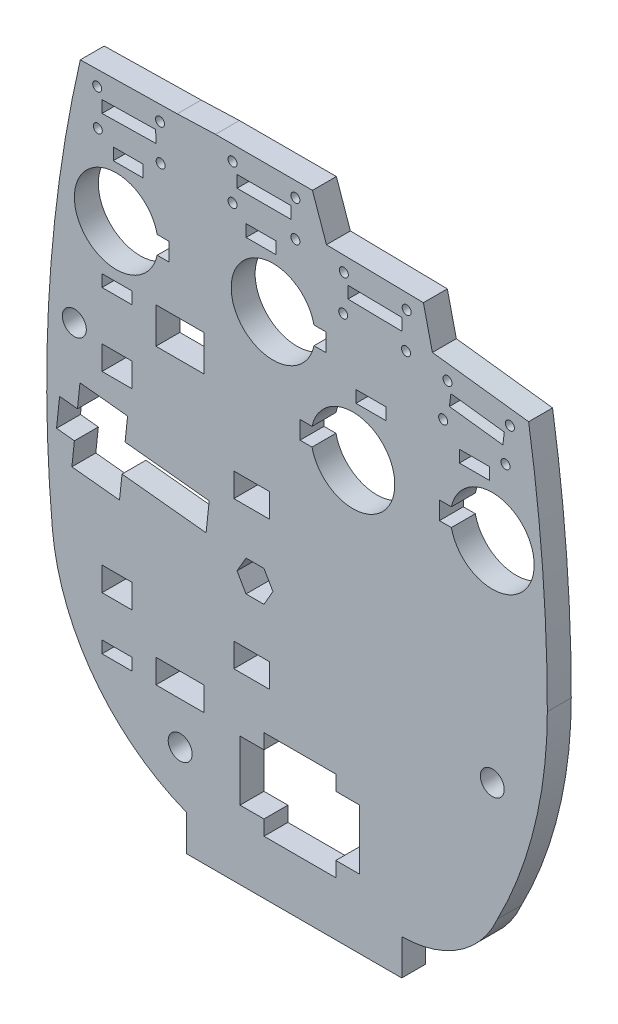
SolidWorks part; units mm, degrees
ref_plane "Front Plane" through (0, 0, 0) normal (0, 0, 1) x (1, 0, 0)
ref_plane "Top Plane" through (0, 0, 0) normal (0, 1, 0) x (1, 0, 0)
ref_plane "Right Plane" through (0, 0, 0) normal (1, 0, 0) x (0, 0, -1)
sketch "Sketch1" plane through (0, 0, 0) normal (0, 0, 1) x (1, 0, 0)
  line L0 (-4.5, 78.51) -> (-4.5, 76.51)
  line L1 (4.5, 78.51) -> (-4.5, 78.51)
  line L2 (-12.9786, -18) -> (-12.9786, -24)
  line L3 (-9.666, 24.0723) -> (-9.153, 28.9531)
  line L4 (-4.5, 76.51) -> (4.5, 76.51)
  line L5 (4.5, 76.51) -> (4.5, 78.51)
  line L6 (-34.6568, 26.6989) -> (-34.1438, 31.5798)
  line L7 (10.3588, 63.1512) -> (10.3588, 60.1512)
  line L8 (-8.1, 82.51) -> (8.1, 82.51)
  line L9 (8.3588, 63.1512) -> (10.3588, 63.1512)
  line L10 (10.4412, 75.8064) -> (26.6388, 75.5236)
  line L11 (32.6473, 57.3216) -> (37.6473, 57.3216)
  line L12 (0, 0) -> (-22.59, 0) construction
  line L13 (10.3588, 60.1512) -> (8.3588, 60.1512)
  line L14 (-17.8416, 63.1512) -> (-15.8416, 63.1512)
  line L15 (-15.8416, 63.1512) -> (-15.8416, 60.1512)
  line L16 (-15.8416, 60.1512) -> (-17.8416, 60.1512)
  line L17 (32.6473, 55.3216) -> (37.6473, 55.3216)
  line L18 (37.6473, 55.3216) -> (37.6473, 57.3216)
  line L19 (32.6473, 57.3216) -> (32.6473, 55.3216)
  line L20 (-27.0893, 78.0609) -> (-18.0907, 78.2179)
  line L21 (-27.0893, 78.0609) -> (-27.0544, 76.0612)
  line L22 (-10.0543, 52.8756) -> (-18.0543, 52.8756)
  line L23 (-9.153, 28.9531) -> (-23.2041, 30.43)
  line L24 (-27.0544, 76.0612) -> (-18.0558, 76.2182)
  line L25 (-24.1352, 21.571) -> (-32.0914, 22.4072)
  line L26 (-32.0914, 22.4072) -> (-31.6733, 26.3853)
  line L27 (-23.7171, 25.5491) -> (-9.666, 24.0723)
  line L28 (-18.0558, 76.2182) -> (-18.0907, 78.2179)
  line L29 (15.3631, 57.3216) -> (20.3631, 57.3216)
  line L30 (15.3631, 55.3216) -> (20.3631, 55.3216)
  line L31 (-12.9786, -24) -> (23.0214, -24)
  line L32 (20.3631, 55.3216) -> (20.3631, 57.3216)
  line L33 (23.0214, -24) -> (23.0214, -18)
  line L34 (15.3631, 57.3216) -> (15.3631, 55.3216)
  line L35 (-2.9786, 72.1512) -> (2.0214, 72.1512)
  line L36 (14.0671, 71.7425) -> (14.0322, 69.7428)
  line L37 (14.0322, 69.7428) -> (23.0308, 69.5857)
  line L38 (8.0257, 48.3216) -> (6.0257, 48.3216)
  line L39 (-2.9786, 70.1512) -> (2.0214, 70.1512)
  line L40 (23.0657, 71.5854) -> (14.0671, 71.7425)
  line L41 (6.0257, 48.3216) -> (6.0257, 45.3216)
  line L42 (23.0308, 69.5857) -> (23.0657, 71.5854)
  line L43 (-22.59, 0) -> (-22.59, 82.14) construction
  line L44 (2.0214, 70.1512) -> (2.0214, 72.1512)
  line L45 (18.54, 75.665) -> (18.5922, 78.6567) construction
  line L46 (-2.9786, 72.1512) -> (-2.9786, 70.1512)
  line L47 (40.1589, 63.5612) -> (31.226, 64.6585)
  line L48 (6.0257, 45.3216) -> (8.0257, 45.3216)
  line L49 (29.3099, 45.3216) -> (31.3099, 45.3216)
  line L50 (29.3099, 48.3216) -> (29.3099, 45.3216)
  line L51 (31.3099, 48.3216) -> (29.3099, 48.3216)
  line L52 (-22.786, 34.408) -> (-30.7422, 35.2443)
  line L53 (31.226, 64.6585) -> (30.9822, 62.6734)
  line L54 (-25.179, 72.1512) -> (-20.179, 72.1512)
  line L55 (-30.6888, 81.9986) -> (-14.4912, 82.2814)
  line L56 (44.2196, 67.0924) -> (28.1404, 69.0676)
  line L57 (-25.179, 70.1512) -> (-20.179, 70.1512)
  line L58 (30.9822, 62.6734) -> (39.915, 61.5761)
  line L59 (-20.179, 70.1512) -> (-20.179, 72.1512)
  line L60 (-25.179, 72.1512) -> (-25.179, 70.1512)
  line L61 (39.915, 61.5761) -> (40.1589, 63.5612)
  line L62 (-34.6568, 26.6989) -> (-31.6733, 26.3853)
  line L63 (-4, -2.5) -> (0, -2.5)
  line L64 (12, 0) -> (0, 0)
  line L65 (12, 0) -> (12, -2.5)
  line L66 (12, -15) -> (0, -15)
  line L67 (-30.7422, 35.2443) -> (-31.1603, 31.2662)
  line L68 (-23.2041, 30.43) -> (-22.786, 34.408)
  line L69 (-34.1438, 31.5798) -> (-31.1603, 31.2662)
  line L70 (-24.1352, 21.571) -> (-23.7171, 25.5491)
  line L71 (16, -7.5) -> (38.9999, -7.5) construction
  line L72 (0, -15) -> (0, -12.5)
  line L73 (-4, -12.5) -> (-4, -2.5)
  line L74 (-4, -12.5) -> (0, -12.5)
  line L75 (0, -2.5) -> (0, 0)
  line L76 (0, 0) -> (0, 82.51) construction
  line L77 (-22.0543, 52.8756) -> (-27.0543, 52.8756)
  line L78 (-10.0543, -2.1244) -> (-18.0543, -2.1244)
  line L79 (-22.0543, -2.1244) -> (-27.0543, -2.1244)
  line L80 (0, 0) -> (18.54, 0) construction
  line L81 (16, -12.5) -> (12, -12.5)
  line L82 (16, -12.5) -> (16, -2.5)
  line L83 (16, -2.5) -> (12, -2.5)
  line L84 (12, -12.5) -> (12, -15)
  line L85 (-9.4095, 26.5127) -> (6.9858, 24.7895) construction
  line L86 (0, 23.7547) -> (-3, 23.7547)
  line L87 (-3, 23.7547) -> (-4.5, 21.1566)
  line L88 (-4.5, 21.1566) -> (-3, 18.5585)
  line L89 (18.54, 0) -> (18.54, 75.665) construction
  line L90 (0, 0) -> (36.18, 0) construction
  line L91 (36.18, 0) -> (36.18, 68.08) construction
  line L92 (28.1404, 69.0676) -> (26.6388, 75.5236)
  line L93 (10.4412, 75.8064) -> (8.1, 82.51)
  line L94 (-8.1, 82.51) -> (-14.4912, 82.2814)
  line L95 (-34.6568, 26.6989) -> (47.343, 26.6989) construction
  line L96 (35.6924, 64.1098) -> (36.1801, 68.08) construction
  line L97 (-3, 18.5585) -> (0, 18.5585)
  line L98 (0, 18.5585) -> (1.5, 21.1566)
  line L99 (1.5, 21.1566) -> (0, 23.7547)
  line L100 (0, 18.5585) -> (-3, 23.7547) construction
  line L101 (0, 23.7547) -> (-3, 18.5585) construction
  line L102 (38.1473, 11.8216) -> (-35.3527, 11.8216) construction
  line L104 (0.9634, 10.717) -> (0.9634, 6.717)
  line L105 (0.9634, 6.717) -> (-5.0366, 6.717)
  line L106 (-5.0366, 6.717) -> (-5.0366, 10.717)
  line L107 (-5.0366, 10.717) -> (0.9634, 10.717)
  line L108 (-5.0366, 31.3356) -> (0.9634, 31.3356)
  line L109 (-5.0366, 35.3356) -> (-5.0366, 31.3356)
  line L110 (0.9634, 35.3356) -> (-5.0366, 35.3356)
  line L111 (0.9634, 31.3356) -> (0.9634, 35.3356)
  line L119 (-22.0543, -0.1244) -> (-27.0543, -0.1244)
  line L121 (-10.0543, 1.8756) -> (-10.0543, -2.1244)
  line L123 (-10.0543, 52.8756) -> (-10.0543, 46.8756)
  line L124 (-10.0543, 1.8756) -> (-18.0543, 1.8756)
  line L125 (-18.0543, 1.8756) -> (-18.0543, -2.1244)
  line L128 (-22.0543, -0.1244) -> (-22.0543, -2.1244)
  line L129 (-27.0543, -0.1244) -> (-27.0543, -2.1244)
  line L131 (-10.0543, 46.8756) -> (-18.0543, 46.8756)
  line L132 (-27.0543, 52.8756) -> (-27.0543, 50.8756)
  line L133 (-18.0543, 46.8756) -> (-18.0543, 52.8756)
  line L135 (-22.0543, 6.717) -> (-22.0543, 10.717)
  line L136 (-22.0543, 10.717) -> (-27.0543, 10.717)
  line L137 (-27.0543, 50.8756) -> (-22.0543, 50.8756)
  line L138 (-22.0543, 52.8756) -> (-22.0543, 50.8756)
  line L139 (-27.0543, 10.717) -> (-27.0543, 6.717)
  line L140 (-27.0543, 6.717) -> (-22.0543, 6.717)
  line L141 (-27.0543, 38.7272) -> (-22.0543, 38.7272)
  line L142 (-22.0543, 38.7272) -> (-22.0543, 42.7272)
  line L143 (-22.0543, 42.7272) -> (-27.0543, 42.7272)
  line L144 (-27.0543, 42.7272) -> (-27.0543, 38.7272)
  arc A0 (-35.3527, 11.8216) -> (-30.6888, 81.9986) centre (186.4896, 32.3217) cw
  circle A1 centre (-1.5, 21.1566) radius 4.5 construction
  arc A2 (8.3588, 63.1512) -> (8.3588, 60.1512) centre (1.5214, 61.6512) ccw
  arc A3 (8.0257, 45.3216) -> (8.0257, 48.3216) centre (14.8631, 46.8216) ccw
  arc A4 (-17.8416, 63.1512) -> (-17.8416, 60.1512) centre (-24.679, 61.6512) ccw
  arc A5 (31.3099, 45.3216) -> (31.3099, 48.3216) centre (38.1473, 46.8216) ccw
  arc A6 (23.0214, -18) -> (38.9999, -7.5) centre (23.0214, -0.5923) ccw
  arc A7 (47.343, 26.6989) -> (38.9999, -7.5) centre (-26.9196, 26.6989) cw
  arc A8 (-35.3527, 11.8216) -> (-12.9786, -18) centre (0.0716, 15.0951) ccw
  arc A9 (47.343, 26.6989) -> (44.2196, 67.0924) centre (-215.4084, 26.6989) ccw
  circle A11 centre (38.1473, 11.8216) radius 2
  circle A12 centre (-14, -9.1244) radius 2
  circle A18 centre (-5.25, 80.01) radius 0.75
  circle A22 centre (-31.6815, 43.4564) radius 2
  circle A49 centre (5.25, 80.01) radius 0.75
  circle A50 centre (5.25, 74.01) radius 0.75
  circle A51 centre (-5.25, 74.01) radius 0.75
  circle A52 centre (-27.8654, 79.5475) radius 0.75
  circle A53 centre (-17.367, 79.7308) radius 0.75
  circle A54 centre (-27.7606, 73.5485) radius 0.75
  circle A55 centre (-17.2622, 73.7317) radius 0.75
  circle A56 centre (23.7371, 67.073) radius 0.75
  circle A57 centre (13.2387, 67.2562) radius 0.75
  circle A58 centre (23.8418, 73.0721) radius 0.75
  circle A59 centre (13.3434, 73.2553) radius 0.75
  circle A60 centre (29.9337, 60.2893) radius 0.75
  circle A61 centre (41.0861, 64.9584) radius 0.75
  circle A62 centre (30.6645, 66.2389) radius 0.75
  circle A63 centre (40.3553, 59.0092) radius 0.75
  dimension "D1" = 4
  dimension "D2" = 1.5
  dimension "D11" = 1.5214
  dimension "D12" = 2.0214
  dimension "D16" = 6.0257
  dimension "D17" = 4
  dimension "D18" = 8.3588
  dimension "D19" = 22.59
  dimension "D22" = 4
  dimension "D23" = 18.54
  dimension "D24" = 75.665
  dimension "D25" = 12
  dimension "D35" = 4
  dimension "D36" = 16.2
  dimension "D37" = 2
  dimension "D38" = 29.3099
  dimension "D39" = 9
  dimension "D40" = 46.8216
  dimension "D43" = 3.1334
  dimension "D44" = 24.679
  dimension "D45" = 9
  dimension "D46" = 0.7292
  dimension "D47" = 4.9078
  dimension "D49" = 5.0366
  dimension "D51" = 9.666
  dimension "D55" = 24
  dimension "D56" = 15.8416
  dimension "D13" = 3.7911
  dimension "D58" = 2.5241
  dimension "D59" = 18.0543
  dimension "D60" = 2.797
  dimension "D61" = 2.551
  dimension "D63" = 22.0543
  dimension "D64" = 2.4516
  dimension "D65" = 2.9021
  dimension "D52" = 10.0543
  dimension "D48" = 25.1285
  dimension "D53" = 12.9786
  dimension "D57" = 4
  dimension "D69" = 2.8757
  dimension "D70" = 2.5506
  dimension "D71" = 1.8756
  dimension "D79" = 43.4564
  dimension "D82" = 55.3216
  dimension "D67" = 2.5
  dimension "D68" = 31.6815
  dimension "D5" = 7
  dimension "D29" = 3.7911
  dimension "D10" = 0.9634
  dimension "D14" = 82.51
  dimension "D15" = 3
  dimension "D20" = 10
  dimension "D21" = 82.14
  dimension "D26" = 15.3631
  dimension "D27" = 2.5
  dimension "D28" = 0
  dimension "D30" = 20.3631
  dimension "D31" = 36.18
  dimension "D32" = 68.08
  dimension "D33" = 23.0214
  dimension "D34" = 4
  dimension "D41" = 14.8631
  dimension "D42" = 32.6473
  dimension "D50" = 9.153
  dimension "D54" = 14
  dimension "D62" = 20.179
  dimension "D66" = 2.85
  dimension "D72" = 6.717
  dimension "D73" = 2.4511
  dimension "D74" = 2.8234
  dimension "D75" = 11.8216
  dimension "D76" = 21.571
  dimension "D77" = 31.3356
  dimension "D80" = 45.3216
  dimension "D81" = 46.8756
  dimension "D84" = 60.1512
  dimension "D86" = 70.1512
  dimension "D93" = 9.1244
extrude "Boss-Extrude1" add sketch "Sketch1" along normal blind 4
equation "\"D14@Sketch1\"= \"HL@parametersSketch@prostheticParameters.SLDPRT\" * 0.446'Mioddle Base Frame "
equation "\"D19@Sketch1\"= \"HB@parametersSketch@prostheticParameters.SLDPRT\" * 0.251'Index Base Frame X"
equation "\"D21@Sketch1\"= \"HL@parametersSketch@prostheticParameters.SLDPRT\" * 0.444'Index Base Frame Y"
equation "\"D23@Sketch1\"= \"HB@parametersSketch@prostheticParameters.SLDPRT\" * 0.206'Ring Base Frame X"
equation "\"D24@Sketch1\"= \"HL@parametersSketch@prostheticParameters.SLDPRT\" * 0.409'Ring Base Frame Y"
equation "\"D31@Sketch1\"= \"HB@parametersSketch@prostheticParameters.SLDPRT\" * 0.402'Pinky Base Frame X"
equation "\"D32@Sketch1\"= \"HL@parametersSketch@prostheticParameters.SLDPRT\" * 0.368'Pinky Base Frame Y"
equation "\"D36@Sketch1\"= \"fingerWidth@parametersSketch@prostheticParameters.SLDPRT\"'Fingers Width"
equation "\"D76@Sketch1\"= \"HL@parametersSketch@prostheticParameters.SLDPRT\" * 0.1166'Hole Thumb Y"
equation "\"D51@Sketch1\"= \"HB@parametersSketch@prostheticParameters.SLDPRT\" * 0.1074'Hole Thumb X1"
equation "\"D50@Sketch1\" = \"HB@parametersSketch@prostheticParameters.SLDPRT\" * 0.1017'Hole Thumb X2"
